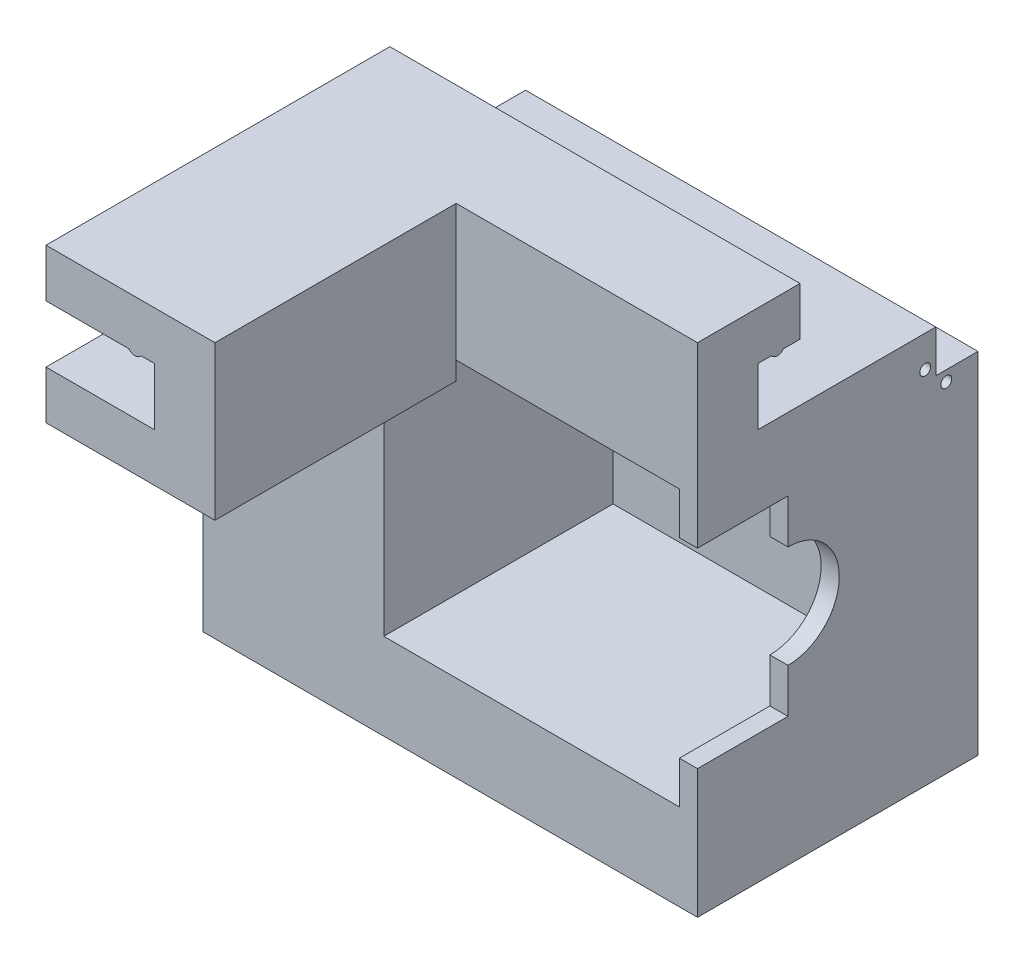
SolidWorks part; units mm, degrees
ref_plane "Front Plane" through (0, 0, 0) normal (0, 0, 1) x (1, 0, 0)
ref_plane "Top Plane" through (0, 0, 0) normal (0, 1, 0) x (1, 0, 0)
ref_plane "Right Plane" through (0, 0, 0) normal (1, 0, 0) x (0, 0, -1)
sketch "Sketch1" plane through (0, 0, 0) normal (0, 0, 1) x (1, 0, 0)
  line L0 (0, 0) -> (-18, 0)
  line L1 (-18, 0) -> (-18, -8)
  line L2 (-18, -8) -> (0, -8)
  line L3 (0, -8) -> (0, -17.5)
  line L4 (0, -17.5) -> (-18, -17.5)
  line L5 (-18, -17.5) -> (-18, -25.5)
  line L6 (-18, -25.5) -> (10, -25.5)
  line L7 (10, -25.5) -> (10, 0)
  line L8 (10, 0) -> (0, 0)
  arc A0 (-4.25, -8) -> (-2.25, -8) centre (-3.25, -7.25) ccw
  point P13 (-3.25, -8.5)
  dimension "D7" = 3.25
  dimension "D1" = 18
  dimension "D2" = 9.5
  dimension "D3" = 8
  dimension "D4" = 8
  dimension "D5" = 10
  dimension "D6" = 9
  dimension "D8" = 1
  dimension "D9" = 28
extrude "Boss-Extrude1" add sketch "Sketch1" along normal blind 50 contours L2 A0 | L7 L8 L0 L1 L2 L3 L4 L5 L6 region at (5, -0.3787, 0) region at (-3.25, -8.2039, 0)
sketch "Sketch2" plane through (0, 0, 0) normal (1, 0, 0) x (0, 0, -1)
  line L9 (0, 0) -> (0, -50) construction
  line L10 (7, -8) -> (0, -8)
  line L11 (0, -17.5) -> (7, -17.5)
  line L12 (0, -8) -> (0, -17.5)
  line L13 (7, -17.5) -> (7, -25.5)
  line L14 (7, -25.5) -> (-10, -25.5)
  line L15 (-10, -25.5) -> (-10, 0)
  line L16 (-10, 0) -> (0, 0)
  line L17 (0, 0) -> (7, 0)
  line L18 (7, 0) -> (7, -8)
  arc A1 (4.25, -8) -> (2.25, -8) centre (3.25, -7.25) cw
  dimension "D13" = 1.25
  dimension "D2" = 17
  dimension "D3" = 3.25
  dimension "D4" = 25.5
  dimension "D5" = 1
  dimension "D6" = 9.5
  dimension "D7" = 8
  dimension "D8" = 8
  dimension "D9" = 10
  dimension "D10" = 10
  dimension "D11" = 50
  dimension "D12" = 7
  dimension "D16" = 0.75
extrude "Boss-Extrude2" add sketch "Sketch2" along normal blind 50 contours L17 L9 L10 L18 | L9 L16 L15 L14 L12 | L11 L9 L14 L13 | A1 L10 region at (0, -4, -3.5) region at (0, -12.75, 5) region at (0, -21.5, -3.5) region at (0, -8.2039, -3.25)
extrude "Boss-Extrude3" add sketch "Sketch2<3>" against normal up to surface (18 mm away) contours L17 L9 L10 L18 | L11 L9 L14 L13 region at (0, -4, -3.5) region at (0, -21.5, -3.5) up to face at (-18, -4, 25)
sketch "Sketch2<3>" plane through (0, 0, 0) normal (1, 0, 0) x (0, 0, -1) same geometry as "Sketch2"
sketch "Sketch3" plane through (50, 0, 0) normal (1, 0, 0) x (0, 0, -1)
  line L0 (0, -17.5) -> (36.5, -17.5)
  line L1 (0, -25.5) -> (0, -88.5)
  line L2 (7, -25.5) -> (-10, -25.5) construction
  line L3 (0, -17.5) -> (0, -25.5)
  line L4 (36.5, -17.5) -> (36.5, -88.5)
  line L5 (36.5, -88.5) -> (0, -88.5)
  line L6 (0, -17.5) -> (-10, -17.5)
  line L7 (-10, -25.5) -> (-10, 0) construction
  line L8 (-10, -17.5) -> (-10, -88.5)
  line L9 (-10, -88.5) -> (0, -88.5)
  line M3 (-10, 0) -> (-10, -25.5)
  line M4 (-10, -25.5) -> (7, -25.5)
  line M5 (7, -25.5) -> (7, -17.5)
  line M6 (7, -17.5) -> (0, -17.5)
  dimension "D1" = 36.5
  dimension "D2" = 63
ref_plane "Wall" through (-32, 0, 0) normal (-1, 0, 0) x (0, 0, 1)
extrude "Boss-Extrude4" add sketch "Sketch3" against normal up to surface (82 mm away) contours L5 L4 L0 L1 M5 M4 | L8 L9 L1 M4 | L3 M6 M4 M5 | L3 L6 M3 M4 region at (50, -21.5, -3.5) region at (50, -21.5, 5) region at (50, -53.6957, -18.5758) region at (50, -57, 5) up to plane "Wall"
fillet "Fillet1" radius 5 3 edges at (-32, -53, -36.5) (-32, -17.5, -13.25) (9, -17.5, -36.5)
sketch "Sketch4" plane through (0, -88.5, 0) normal (0, -1, 0) x (1, 0, 0)
  line L0 (50, 10) -> (50, -19.5)
  line L1 (50, -36.5) -> (50, 10) construction
  line L2 (50, -19.5) -> (1, -19.5)
  line L3 (1, -19.5) -> (1, 10)
  line L4 (-18, 10) -> (10, 10) construction
  line L5 (1, 10) -> (50, 10)
  line L6 (-32, -31.5) -> (-32, 10) construction
  line L7 (-27, -36.5) -> (50, -36.5) construction
  dimension "D1" = 33
  dimension "D2" = 17
extrude "Cut-Extrude1" cut sketch "Sketch4" against normal up to surface (63 mm away) up to face at (-4, -25.5, 30)
sketch "Sketch5" plane through (50, 0, 0) normal (1, 0, 0) x (0, 0, -1)
  line L0 (-10, -36.5) -> (19.5, -36.5)
  line L1 (-10, -25.5) -> (-10, -88.5) construction
  line L2 (19.5, -25.5) -> (19.5, -88.5) construction
  line L3 (19.5, -36.5) -> (19.5, -77.5)
  line L4 (19.5, -77.5) -> (-10, -77.5)
  line L5 (-10, -77.5) -> (-10, -36.5)
  line L6 (0, -17.5) -> (31.5, -17.5) construction
  line L7 (-10, -36.5) -> (-10, -25.5)
  line L8 (-10, -25.5) -> (19.5, -25.5)
  line L9 (19.5, -25.5) -> (19.5, -36.5)
  line L10 (-10, -77.5) -> (-10, -88.5)
  line L11 (-10, -88.5) -> (19.5, -88.5)
  line L12 (19.5, -88.5) -> (19.5, -77.5)
  line M3 (-10, -25.5) -> (19.5, -25.5)
  line M4 (19.5, -25.5) -> (19.5, -88.5)
  dimension "D1" = 19
  dimension "D2" = 41
extrude "Boss-Extrude5" add sketch "Sketch5" against normal up to surface (49 mm away) contours L7 L0 M4 M3 | L10 L11 L4 M4 region at (50, -31, -4.75) region at (50, -83, -4.75) up to face at (1, -57, -4.75)
sketch "Sketch7" plane through (0, 0, 10) normal (0, 0, 1) x (1, 0, 0)
  line L0 (1, -36.5) -> (27, -36.5)
  line L1 (1, -36.5) -> (50, -36.5) construction
  line L2 (27, -36.5) -> (27, -26.5)
  line L3 (27, -26.5) -> (50, -26.5)
  line L4 (50, -36.5) -> (50, 0) construction
  line L5 (50, -26.5) -> (50, -88.5)
  line L6 (50, -88.5) -> (27, -88.5)
  line L7 (-32, -88.5) -> (50, -88.5) construction
  line L8 (27, -88.5) -> (27, -77.5)
  line L9 (1, -77.5) -> (50, -77.5) construction
  line L10 (27, -77.5) -> (1, -77.5)
  line L11 (1, -77.5) -> (1, -36.5)
  dimension "D1" = 26
  dimension "D2" = 26
  dimension "D3" = 10
extrude "Cut-Extrude2" cut sketch "Sketch7" against normal up to surface (29.5 mm away) up to face at (25.5, -57, -19.5)
sketch "Sketch6" plane through (27, 0, 0) normal (1, 0, 0) x (0, 0, -1)
  line L0 (-10, -36.5) -> (-10, -77.5) construction
  line L1 (36.5, -57) -> (-10, -57)
  line L2 (-1, -57) -> (19.5, -57)
  line L4 (9.25, -57) -> (9.25, -88.5)
  line L5 (36.5, -88.5) -> (19.5, -88.5) construction
  line L6 (4.25, -81.5) -> (14.25, -81.5)
  line L7 (36.5, -22.5) -> (36.5, -88.5) construction
  line L8 (0, -17.5) -> (31.5, -17.5) construction
  line L9 (19.5, -26.5) -> (19.5, -88.5) construction
  circle A0 centre (4.25, -81.5) radius 1.75
  circle A1 centre (14.25, -81.5) radius 1.75
  circle A2 centre (4.25, -81.5) radius 0.75
  circle A3 centre (14.25, -81.5) radius 0.75
  circle A4 centre (14.25, -32.5) radius 0.75
  circle A5 centre (14.25, -32.5) radius 1.75
  circle A6 centre (4.25, -32.5) radius 0.75
  circle A7 centre (4.25, -32.5) radius 1.75
  point P16 (9.25, -81.5)
  dimension "D4" = 3.5
  dimension "D5" = 1.5
  dimension "D6" = 1.5
  dimension "D7" = 3.5
  dimension "D1" = 24.5
  dimension "D2" = 24.5
  dimension "D3" = 10
  dimension "D8" = 20.5
  dimension "D9" = 39.5
  dimension "D10" = 0
extrude "Cut-Extrude3" cut sketch "Sketch6" against normal blind 5 contours A7 A6 | A6 | A5 A4 | A4 | A2 A0 | A2 | A3 A1 | A3 region at (27, -81.5, -2.5495) region at (27, -80.7712, -14.25) region at (27, -79.7995, -14.25) region at (27, -81.5, -3.5212) region at (27, -32.5, -14.25) region at (27, -32.5, -12.5495) region at (27, -32.5, -4.25) region at (27, -32.5, -2.5495)
extrude "Cut-Extrude4" cut sketch "Sketch6<6>" against normal blind 15 contours A6 | A4 | A2 | A3 region at (27, -81.5, -3.5212) region at (27, -32.5, -14.25) region at (27, -32.5, -4.25)
sketch "Sketch6<6>" plane through (27, 0, 0) normal (1, 0, 0) x (0, 0, -1) same geometry as "Sketch6"
sketch "Sketch8" plane through (0, 0, -7) normal (0, 0, -1) x (-1, 0, 0)
  line L0 (0, -8) -> (18, -8)
  line L1 (18, -8) -> (18, -17.5)
  line L2 (-50, -17.5) -> (27, -17.5) construction
  line L3 (18, -17.5) -> (0, -17.5)
  line L4 (0, -17.5) -> (0, -8)
extrude "Cut-Extrude5" cut sketch "Sketch8" against normal blind 40
sketch "Sketch9" plane through (-18, 0, 0) normal (-1, 0, 0) x (0, 0, 1)
  line L0 (-7, -8) -> (0, -8)
  line L1 (0, -8) -> (0, -17.5)
  line L2 (0, -17.5) -> (-7, -17.5)
  line L3 (-31.5, -17.5) -> (10, -17.5) construction
  line L4 (-7, -17.5) -> (-7, -8)
extrude "Cut-Extrude6" cut sketch "Sketch9" against normal blind 45
sketch "Sketch10" plane through (0, 0, 10) normal (0, 0, 1) x (1, 0, 0)
  line L0 (1, -36.5) -> (11, -36.5)
  line L1 (1, -36.5) -> (27, -36.5) construction
  line L2 (11, -36.5) -> (11, -26.5)
  line L3 (11, -26.5) -> (1, -26.5)
  line L4 (1, -26.5) -> (1, -36.5)
  dimension "D1" = 10
  dimension "D2" = 10
extrude "Cut-Extrude7" cut sketch "Sketch10" against normal up to surface (29.5 mm away) up to face at (26.25, -57.25, -19.5)
sketch "Sketch11" plane through (0, 0, -19.5) normal (0, 0, 1) x (1, 0, 0)
  line L1 (27, -88.5) -> (50, -88.5) construction
  line L2 (37, -88.5) -> (50, -88.5)
  line L3 (50, -88.5) -> (50, -26.5)
  line L4 (50, -26.5) -> (37, -26.5)
  line L5 (50, -26.5) -> (27, -26.5) construction
  line L8 (37, -26.5) -> (37, -88.5)
  line L9 (27, -26.5) -> (27, -36.5) construction
  line L10 (37, -33.5) -> (50, -33.5)
  line L11 (37, -81.5) -> (50, -81.5)
  line M5 (27, -88.5) -> (50, -88.5)
  line M6 (50, -88.5) -> (50, -26.5)
  dimension "D1" = 10
  dimension "D2" = 7
  dimension "D3" = 7
extrude "Cut-Extrude8" cut sketch "Sketch11" against normal through all contours L8 L11 L3 L10 | L11 L8 M5 M6 region at (43.5, -85, -19.5) region at (43.5, -57.5, -19.5)
sketch "Sketch12" plane through (0, -88.5, 0) normal (0, -1, 0) x (1, 0, 0)
  line L0 (-32, -26.5) -> (-24, -26.5)
  line L1 (-32, -31.5) -> (-32, 10) construction
  line L2 (-24, -26.5) -> (-24, -36.5)
  line L3 (-27, -36.5) -> (37, -36.5) construction
  line L4 (-32, -26.5) -> (-32, -36.5)
  line L5 (-32, -36.5) -> (-24, -36.5)
  dimension "D1" = 8
  dimension "D2" = 10
extrude "Cut-Extrude9" cut sketch "Sketch12" against normal through all
sketch "Sketch13" plane through (-32, 0, 0) normal (-1, 0, 0) x (0, 0, 1)
  line L4 (-26.5, -17.5) -> (-36.5, -17.5)
  line L5 (-36.5, -17.5) -> (-36.5, -23.5)
  line L6 (-36.5, -23.5) -> (-26.5, -23.5)
  line L7 (-26.5, -17.5) -> (-26.5, -88.5) construction
  line L8 (-26.5, -23.5) -> (-26.5, -17.5)
  dimension "D1" = 6
  dimension "D2" = 10
extrude "Cut-Extrude10" cut sketch "Sketch13" against normal up to surface (14 mm away) up to face at (-18, -21.5, 30)
sketch "Sketch14" plane through (0, 0, 10) normal (0, 0, 1) x (1, 0, 0)
  line L10 (10, -17.5) -> (16, -17.5)
  line L11 (10, -25.5) -> (10, 0) construction
  line L12 (16, -17.5) -> (16, -23.5)
  line L13 (16, -23.5) -> (10, -23.5)
  line L14 (10, -23.5) -> (10, -17.5)
  dimension "D1" = 6
  dimension "D2" = 6
sketch "Sketch15" plane through (0, 0, -26.5) normal (0, 0, -1) x (-1, 0, 0)
  line L0 (18, -23.5) -> (18, -17.5)
  line L1 (18, -17.5) -> (32, -17.5)
  line L2 (32, -5.225) -> (32, 5.225) construction
  line L3 (32, -17.5) -> (32, -23.5)
  line L4 (32, -22.5) -> (32, -88.5) construction
  line L5 (32, -23.5) -> (18, -23.5)
extrude "Cut-Extrude11" cut sketch "Sketch15" against normal through all
fillet "Fillet2" radius 3 3 edges at (-28, -23.5, -26.5) (-24, -56, -26.5) (-24, -23.5, -31.5)
ref_plane "Adjustment" through (0, 0, -20) normal (0, 0, 1) x (1, 0, 0)
sketch "Sketch17" plane through (0, 0, 10) normal (0, 0, 1) x (1, 0, 0)
  line L0 (1, -26.5) -> (50, -26.5)
  line L1 (50, -26.5) -> (50, -88.5)
  line L2 (50, -88.5) -> (1, -88.5)
  line L3 (-32, -88.5) -> (27, -88.5) construction
  line L4 (1, -88.5) -> (1, -26.5)
extrude "Boss-Extrude6" add sketch "Sketch17" against normal up to surface (46.5 mm away) up to face at (7.5976, -40.2087, -36.5)
sketch "Sketch18" plane through (0, 0, 10) normal (0, 0, 1) x (1, 0, 0)
  line L0 (5, -88.5) -> (5, -25.5)
  line L1 (-32, -88.5) -> (50, -88.5) construction
  line L2 (-18, -25.5) -> (10, -25.5) construction
  line L3 (5, -25.5) -> (50, -25.5)
  line L4 (50, -88.5) -> (50, 0) construction
  line L5 (50, -25.5) -> (50, -88.5)
  line L6 (50, -88.5) -> (5, -88.5)
  line L7 (-32, -23.5) -> (-32, -88.5) construction
  dimension "D1" = 37
extrude "Cut-Extrude12" cut sketch "Sketch18" against normal up to surface (30 mm away) up to plane "Adjustment"
sketch "Sketch19" plane through (0, 0, -20) normal (0, 0, 1) x (1, 0, 0)
  line L0 (50, -25.5) -> (5, -25.5)
  line L1 (5, -25.5) -> (5, -88.5)
  line L2 (5, -88.5) -> (50, -88.5)
  line L3 (50, -88.5) -> (50, -25.5)
  line L4 (5, -29.5) -> (50, -29.5)
  line L5 (5, -61.15) -> (50, -61.15)
  line M4 (5, -88.5) -> (50, -88.5)
  line M5 (50, -88.5) -> (50, -25.5)
  line M6 (50, -25.5) -> (5, -25.5)
  line M7 (5, -25.5) -> (5, -88.5)
  dimension "D1" = 4
  dimension "D2" = 31.65
extrude "Boss-Extrude7" add sketch "Sketch19" along normal up to surface (30 mm away) contours L4 L3 M7 M6 | L5 M7 M4 M5 region at (27.5, -27.5, -20) region at (27.5, -74.825, -20) up to face at (-15, -45.8333, 10)
sketch "Sketch22" plane through (50, 0, 0) normal (1, 0, 0) x (0, 0, -1)
  line L0 (20, -29.5) -> (20, -61.15)
  line L1 (20, -45.325) -> (5, -45.325)
  line L2 (20, -29.5) -> (-10, -29.5)
  line L3 (-10, -29.5) -> (-10, -61.15)
  line L4 (-10, -61.15) -> (20, -61.15)
  line L5 (5, -61.15) -> (5, -29.5)
  circle A0 centre (5, -45.325) radius 8.5
  point P10 (5, -45.325)
  line M8 (20, -29.5) -> (20, -61.15)
  line M9 (20, -61.15) -> (-10, -61.15)
  dimension "D1" = 17
  dimension "D2" = 15
extrude "Boss-Extrude8" add sketch "Sketch22" against normal blind 3 contours A0 L5 L0 L1 M9 | A0 L1 L2 L5 M8 region at (50, -36.0601, -13.7228) region at (50, -54.5899, -13.7228)
sketch "Sketch24" plane through (0, 0, 10) normal (0, 0, 1) x (1, 0, 0)
  line L0 (-18, -23.5) -> (-32, -23.5)
  line L1 (-32, -23.5) -> (-32, -33.5)
  line L2 (-32, -23.5) -> (-32, -88.5) construction
  line L3 (-32, -33.5) -> (-18, -33.5)
  line L4 (-18, -33.5) -> (-18, -23.5)
  dimension "D1" = 10
extrude "Cut-Extrude15" cut sketch "Sketch24" against normal through all
sketch "Sketch26" plane through (0, 0, -20) normal (0, 0, 1) x (1, 0, 0)
  line L0 (5, -29.5) -> (47, -29.5)
  line L1 (47, -29.5) -> (47, -61.15)
  line L2 (47, -61.15) -> (5, -61.15)
  line L3 (5, -61.15) -> (5, -29.5)
extrude "Cut-Extrude16" cut sketch "Sketch26" against normal blind 8
sketch "Sketch27" plane through (0, -29.5, 0) normal (0, -1, 0) x (1, 0, 0)
  line L0 (5, 10) -> (5, -28)
  line L1 (5, -28) -> (47, -28)
  line L2 (47, -28) -> (47, 10)
  line L3 (5, 10) -> (50, 10) construction
  line L4 (47, 10) -> (5, 10)
extrude "Cut-Extrude17" cut sketch "Sketch27" against normal blind 7
sketch "Sketch28" plane through (0, -61.15, 0) normal (0, 1, 0) x (1, 0, 0)
  line L0 (5, 28) -> (47, 28)
  line L1 (47, 28) -> (47, -10)
  line L2 (5, -10) -> (50, -10) construction
  line L3 (47, -10) -> (5, -10)
  line L4 (5, -10) -> (5, 28)
extrude "Cut-Extrude18" cut sketch "Sketch28" against normal blind 7
sketch "Sketch29" plane through (5, 0, 0) normal (1, 0, 0) x (0, 0, -1)
  line L0 (28, -22.5) -> (-10, -22.5)
  line L1 (-10, -22.5) -> (-10, -68.15)
  line L2 (-10, -68.15) -> (28, -68.15)
  line L3 (28, -68.15) -> (28, -22.5)
extrude "Cut-Extrude19" cut sketch "Sketch29" against normal blind 7
sketch "Sketch30" plane through (50, 0, 0) normal (1, 0, 0) x (0, 0, -1)
  line L0 (-10, -88.5) -> (-10, -82.5)
  line L1 (-10, -88.5) -> (-10, -61.15) construction
  line L2 (-10, -82.5) -> (36.5, -82.5)
  line L3 (36.5, -22.5) -> (36.5, -88.5) construction
  line L4 (36.5, -82.5) -> (36.5, -88.5)
  line L5 (36.5, -88.5) -> (-10, -88.5)
  dimension "D1" = 6
extrude "Cut-Extrude20" cut sketch "Sketch30" against normal through all
sketch "Sketch32" plane through (50, 0, 0) normal (1, 0, 0) x (0, 0, -1)
  line L0 (36.5, -17.5) -> (26, -17.5)
  line L1 (26, -17.5) -> (26, -28)
  line L2 (26, -28) -> (36.5, -28)
  line L3 (36.5, -28) -> (36.5, -17.5)
  line L4 (29.5, -17.5) -> (29.5, -24.5)
  line L5 (29.5, -24.5) -> (36.5, -24.5)
  line L6 (26, -20) -> (27.25, -20)
  line L7 (27.25, -20) -> (27.25, -19)
  line L8 (27.25, -19) -> (26.5, -19)
  line L9 (26.5, -19) -> (26.5, -18.25)
  line L10 (26.5, -18.25) -> (29, -18.25)
  line L11 (29, -18.25) -> (29, -19)
  line L12 (29, -19) -> (28.25, -19)
  line L13 (28.25, -19) -> (28.25, -20)
  line L14 (28.25, -20) -> (29.5, -20)
  line L15 (34.1, -24.5) -> (34.1, -26.35)
  line L16 (34.1, -26.35) -> (33, -26.35)
  line L17 (33, -26.35) -> (33, -27.25)
  line L18 (33, -27.25) -> (36.5, -27.25)
  line L19 (36.5, -27.25) -> (36.5, -26.35)
  line L20 (36.5, -26.35) -> (35.4, -26.35)
  line L21 (35.4, -26.35) -> (35.4, -24.5)
  line L22 (36.15, -26.35) -> (36.15, -27.25)
  line L23 (33.35, -26.35) -> (33.35, -27.25)
  line L24 (26, -21) -> (29.5, -21)
  line L25 (33, -24.5) -> (33, -28)
  line L26 (33, -25.5) -> (36.5, -25.5)
  circle A0 centre (27.75, -22.75) radius 0.75
  circle A1 centre (31.25, -26.25) radius 0.75
  circle A2 centre (27.75, -22.75) radius 0.9
  circle A3 centre (31.25, -26.25) radius 0.9
  point P41 (45.7841, -33.4169)
  point P42 (36.5, -17.5)
  arc M3 (36.5, -22.5) -> (31.5, -17.5) centre (31.5, -22.5) ccw
  line M4 (31.5, -17.5) -> (0, -17.5)
  dimension "D11" = 1.5
  dimension "D12" = 1.8
  dimension "D15" = 1.5
  dimension "D16" = 1.8
  dimension "D1" = 10.5
  dimension "D2" = 10.5
  dimension "D3" = 0.75
  dimension "D4" = 0.5
  dimension "D5" = 0.5
  dimension "D6" = 1.25
  dimension "D7" = 1.25
  dimension "D8" = 1
  dimension "D9" = 1.75
  dimension "D10" = 1.75
  dimension "D13" = 1.75
  dimension "D14" = 1.75
  dimension "D17" = 3.5
  dimension "D18" = 3.5
  dimension "D19" = 3.5
  dimension "D20" = 0.75
  dimension "D21" = 0.35
  dimension "D22" = 0.35
  dimension "D23" = 1.1
  dimension "D24" = 1.1
  dimension "D25" = 1
  dimension "D26" = 0.75
  dimension "D27" = 0.75
  dimension "D28" = 1
  dimension "D29" = 1
  dimension "D30" = 0.85
  dimension "D31" = 0.85
  dimension "D32" = 2.8
  dimension "D33" = 0
extrude "Cut-Extrude21" cut sketch "Sketch32" against normal through all contours L4 L5 L3 M3 M4 region at (50, -21.293, -32.707)
extrude "Cut-Extrude22" cut sketch "Sketch32<3>" against normal blind 6 contours A0 | A2 A0 | A1 | A3 A1 region at (50, -22.75, -27.75) region at (50, -26.25, -31.25) region at (50, -22.75, -26.8755) region at (50, -26.25, -30.3755)
sketch "Sketch32<3>" plane through (50, 0, 0) normal (1, 0, 0) x (0, 0, -1) same geometry as "Sketch32"
